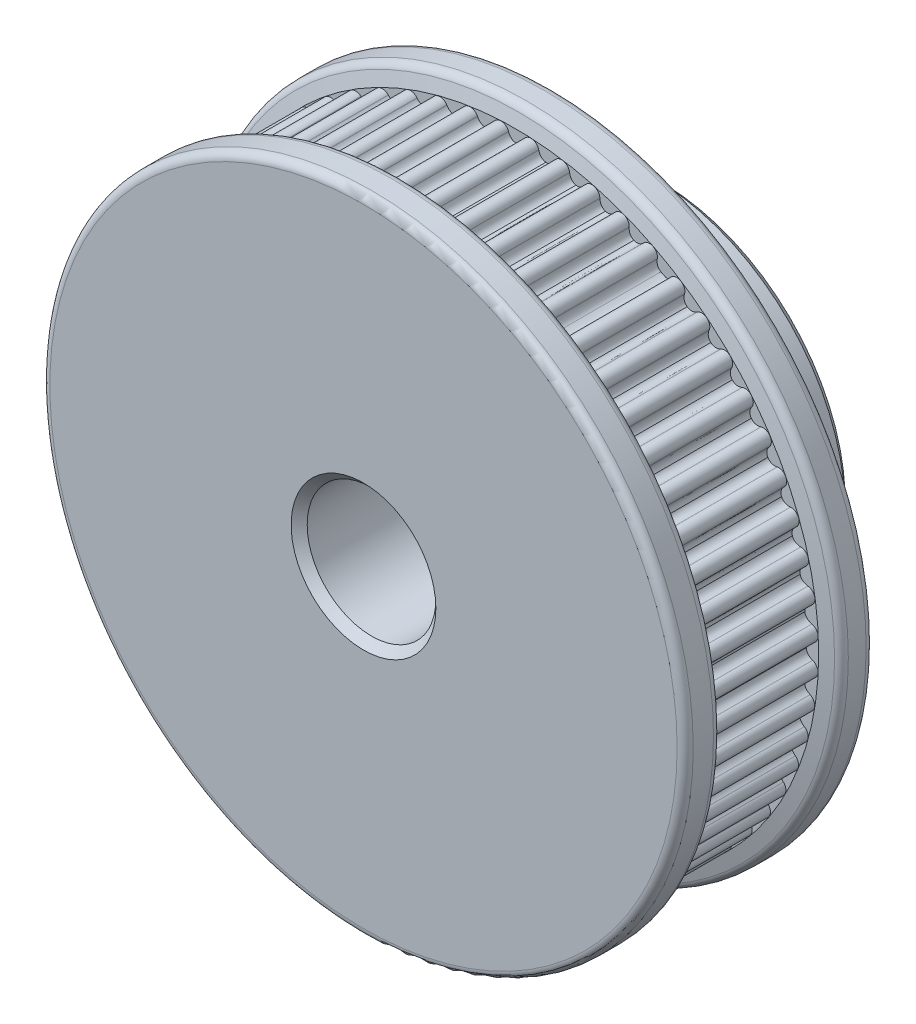
SolidWorks part; units mm, degrees
other "Camera1"
other "Camera2"
other "Camera3"
ref_plane "Front" through (0, 0, 0) normal (0, 0, 1) x (1, 0, 0)
ref_plane "Top" through (0, 0, 0) normal (0, 1, 0) x (1, 0, 0)
ref_plane "Right" through (0, 0, 0) normal (1, 0, 0) x (0, 0, -1)
sketch "Sketch1" plane through (0, 0, 0) normal (1, 0, 0) x (0, 0, -1)
  line L0 (0, 0) -> (-24.4032, 0) construction
  line L1 (0, 4) -> (0, 12)
  line L2 (0, 12) -> (-7, 12)
  line L3 (-7, 12) -> (-7, 18.3141)
  line L4 (-9, 18.85) -> (-16, 18.85)
  line L5 (-18, 18.3141) -> (-18, 4) construction
  line L6 (-18, 4) -> (0, 4)
  line L7 (-7, 18.3141) -> (-6.5483, 20)
  line L9 (-8.6919, 20) -> (-9, 18.85)
  line L10 (-18, 13.3586) -> (-7, 13.3586) construction
  line L11 (-12.5, 18.85) -> (-12.5, 22.0506) construction
  line L12 (-16.3081, 20) -> (-16, 18.85)
  line L14 (-18, 18.3141) -> (-18.4517, 20) construction
  line L15 (-18, 18.3141) -> (-16, 18.85) construction
  line L16 (-9, 18.85) -> (-7, 18.3141) construction
  line L17 (-18.4517, 20) -> (-16.3081, 20)
  line L18 (-8.6919, 20) -> (-6.5483, 20)
  line L19 (-18.4517, 20) -> (-18.4517, 4)
  line L20 (-18.4517, 4) -> (-18, 4)
  circle A0 centre (-3.5, 4) radius 2 construction
  point P22 (-3.5, 12)
  point P24 (-12.5, 13.3586)
  dimension "D9" = 4
  dimension "D1" = 18
  dimension "D2" = 11
  dimension "D3" = 7
  dimension "D4" = 37.7
  dimension "D5" = 40
  dimension "D6" = 15
  dimension "D7" = 24
  dimension "D8" = 8
revolve "Revolve1" add sketch "Sketch1" angle 360 about L0
ref_plane "Plane2" through (0, 0, 9) normal (0, 0, 1) x (1, 0, 0)
ref_plane "Plane3" through (0, 0, 16) normal (0, 0, 1) x (1, 0, 0)
sketch "Sketch3" plane through (0, 0, 9) normal (0, 0, 1) x (1, 0, 0)
  line L0 (0.4895, 18.4804) -> (0.4858, 18.4697)
  line L1 (-0.4323, 18.471) -> (-0.436, 18.4817)
  line L2 (-1.3914, 18.4344) -> (-1.394, 18.4234)
  line L3 (-2.3607, 18.3247) -> (-2.3654, 18.3349)
  line L4 (-3.3107, 18.188) -> (-3.3122, 18.1768)
  line L5 (-4.2632, 17.9775) -> (-4.269, 17.9872)
  line L6 (-5.1937, 17.7423) -> (-5.194, 17.731)
  line L7 (-6.119, 17.4334) -> (-6.1258, 17.4424)
  line L8 (-7.0199, 17.1022) -> (-7.019, 17.0909)
  line L9 (-7.9078, 16.6983) -> (-7.9155, 16.7066)
  line L10 (-8.7691, 16.2747) -> (-8.767, 16.2636)
  line L11 (-9.6099, 15.7803) -> (-9.6184, 15.7877)
  line L12 (-10.4222, 15.269) -> (-10.419, 15.2581)
  line L13 (-11.2067, 14.6893) -> (-11.216, 14.6958)
  line L14 (-11.9612, 14.0959) -> (-11.9568, 14.0855)
  line L15 (-12.6808, 13.4374) -> (-12.6907, 13.4429)
  line L16 (-13.3691, 12.7684) -> (-13.3637, 12.7585)
  line L17 (-14.0159, 12.0383) -> (-14.0263, 12.0427)
  line L18 (-14.6305, 11.301) -> (-14.6241, 11.2917)
  line L19 (-15.1975, 10.5073) -> (-15.2083, 10.5106)
  line L20 (-15.7316, 9.7098) -> (-15.7243, 9.7012)
  line L21 (-16.2125, 8.8612) -> (-16.2236, 8.8633)
  line L22 (-16.6604, 8.0122) -> (-16.6522, 8.0044)
  line L23 (-17.05, 7.118) -> (-17.0612, 7.1189)
  line L24 (-17.4066, 6.2268) -> (-17.3977, 6.22)
  line L25 (-17.7006, 5.2968) -> (-17.7119, 5.2965)
  line L26 (-17.9621, 4.3732) -> (-17.9525, 4.3673)
  line L27 (-18.1573, 3.4175) -> (-18.1685, 3.4161)
  line L28 (-18.3209, 2.4717) -> (-18.3107, 2.4669)
  line L29 (-18.415, 1.5008) -> (-18.426, 1.4983)
  line L30 (-18.4789, 0.5431) -> (-18.4682, 0.5394)
  line L31 (-18.471, -0.4323) -> (-18.4817, -0.436)
  line L32 (-18.4344, -1.3914) -> (-18.4234, -1.394)
  line L33 (-18.3247, -2.3607) -> (-18.3349, -2.3654)
  line L34 (-18.188, -3.3107) -> (-18.1768, -3.3122)
  line L35 (-17.9775, -4.2632) -> (-17.9872, -4.269)
  line L36 (-17.7423, -5.1937) -> (-17.731, -5.194)
  line L37 (-17.4334, -6.119) -> (-17.4424, -6.1258)
  line L38 (-17.1022, -7.0199) -> (-17.0909, -7.019)
  line L39 (-16.6983, -7.9078) -> (-16.7066, -7.9155)
  line L40 (-16.2747, -8.7691) -> (-16.2636, -8.767)
  line L41 (-15.7803, -9.6099) -> (-15.7877, -9.6184)
  line L42 (-15.269, -10.4222) -> (-15.2581, -10.419)
  line L43 (-14.6893, -11.2067) -> (-14.6958, -11.216)
  line L44 (-14.0959, -11.9612) -> (-14.0855, -11.9568)
  line L45 (-13.4374, -12.6808) -> (-13.4429, -12.6907)
  line L46 (-12.7684, -13.3691) -> (-12.7585, -13.3637)
  line L47 (-12.0383, -14.0159) -> (-12.0427, -14.0263)
  line L48 (-11.301, -14.6305) -> (-11.2917, -14.6241)
  line L49 (-10.5073, -15.1975) -> (-10.5106, -15.2083)
  line L50 (-9.7098, -15.7316) -> (-9.7012, -15.7243)
  line L51 (-8.8612, -16.2125) -> (-8.8633, -16.2236)
  line L52 (-8.0122, -16.6604) -> (-8.0044, -16.6522)
  line L53 (-7.118, -17.05) -> (-7.1189, -17.0612)
  line L54 (-6.2268, -17.4066) -> (-6.22, -17.3977)
  line L55 (-5.2968, -17.7006) -> (-5.2965, -17.7119)
  line L56 (-4.3732, -17.9621) -> (-4.3673, -17.9525)
  line L57 (-3.4175, -18.1573) -> (-3.4161, -18.1685)
  line L58 (-2.4717, -18.3209) -> (-2.4669, -18.3107)
  line L59 (-1.5008, -18.415) -> (-1.4983, -18.426)
  line L60 (-0.5431, -18.4789) -> (-0.5394, -18.4682)
  line L61 (0.4323, -18.471) -> (0.436, -18.4817)
  line L62 (1.3914, -18.4344) -> (1.394, -18.4234)
  line L63 (2.3607, -18.3247) -> (2.3654, -18.3349)
  line L64 (3.3107, -18.188) -> (3.3122, -18.1768)
  line L65 (4.2632, -17.9775) -> (4.269, -17.9872)
  line L66 (5.1937, -17.7423) -> (5.194, -17.731)
  line L67 (6.119, -17.4334) -> (6.1258, -17.4424)
  line L68 (7.0199, -17.1022) -> (7.019, -17.0909)
  line L69 (7.9078, -16.6983) -> (7.9155, -16.7066)
  line L70 (8.7691, -16.2747) -> (8.767, -16.2636)
  line L71 (9.6099, -15.7803) -> (9.6184, -15.7877)
  line L72 (10.4222, -15.269) -> (10.419, -15.2581)
  line L73 (11.2067, -14.6893) -> (11.216, -14.6958)
  line L74 (11.9612, -14.0959) -> (11.9568, -14.0855)
  line L75 (12.6808, -13.4374) -> (12.6907, -13.4429)
  line L76 (13.3691, -12.7684) -> (13.3637, -12.7585)
  line L77 (14.0159, -12.0383) -> (14.0263, -12.0427)
  line L78 (14.6305, -11.301) -> (14.6241, -11.2917)
  line L79 (15.1975, -10.5073) -> (15.2083, -10.5106)
  line L80 (15.7316, -9.7098) -> (15.7243, -9.7012)
  line L81 (16.2125, -8.8612) -> (16.2236, -8.8633)
  line L82 (16.6604, -8.0122) -> (16.6522, -8.0044)
  line L83 (17.05, -7.118) -> (17.0612, -7.1189)
  line L84 (17.4066, -6.2268) -> (17.3977, -6.22)
  line L85 (17.7006, -5.2968) -> (17.7119, -5.2965)
  line L86 (17.9621, -4.3732) -> (17.9525, -4.3673)
  line L87 (18.1573, -3.4175) -> (18.1685, -3.4161)
  line L88 (18.3209, -2.4717) -> (18.3107, -2.4669)
  line L89 (18.415, -1.5008) -> (18.426, -1.4983)
  line L90 (18.4789, -0.5431) -> (18.4682, -0.5394)
  line L91 (18.471, 0.4323) -> (18.4817, 0.436)
  line L92 (18.4344, 1.3914) -> (18.4234, 1.394)
  line L93 (18.3247, 2.3607) -> (18.3349, 2.3654)
  line L94 (18.188, 3.3107) -> (18.1768, 3.3122)
  line L95 (17.9775, 4.2632) -> (17.9872, 4.269)
  line L96 (17.7423, 5.1937) -> (17.731, 5.194)
  line L97 (17.4334, 6.119) -> (17.4424, 6.1258)
  line L98 (17.1022, 7.0199) -> (17.0909, 7.019)
  line L99 (16.6983, 7.9078) -> (16.7066, 7.9155)
  line L100 (16.2747, 8.7691) -> (16.2636, 8.767)
  line L101 (15.7803, 9.6099) -> (15.7877, 9.6184)
  line L102 (15.269, 10.4222) -> (15.2581, 10.419)
  line L103 (14.6893, 11.2067) -> (14.6958, 11.216)
  line L104 (14.0959, 11.9612) -> (14.0855, 11.9568)
  line L105 (13.4374, 12.6808) -> (13.4429, 12.6907)
  line L106 (12.7684, 13.3691) -> (12.7585, 13.3637)
  line L107 (12.0383, 14.0159) -> (12.0427, 14.0263)
  line L108 (11.301, 14.6305) -> (11.2917, 14.6241)
  line L109 (10.5073, 15.1975) -> (10.5106, 15.2083)
  line L110 (9.7098, 15.7316) -> (9.7012, 15.7243)
  line L111 (8.8141, 16.2382) -> (8.8162, 16.2492)
  line L112 (7.9639, 16.6835) -> (7.9561, 16.6753)
  line L113 (7.0685, 17.0705) -> (7.0694, 17.0818)
  line L114 (6.1763, 17.4246) -> (6.1695, 17.4156)
  line L115 (5.2454, 17.7159) -> (5.2452, 17.7272)
  line L116 (4.3211, 17.9748) -> (4.3153, 17.9651)
  line L117 (3.3649, 18.1671) -> (3.3634, 18.1783)
  line L118 (2.4186, 18.328) -> (2.4138, 18.3178)
  line L119 (1.4475, 18.4193) -> (1.4449, 18.4303)
  arc A0 (-0.436, 18.4817) -> (-1.3914, 18.4344) centre (-0.9065, 18.3126) ccw
  arc A1 (-2.3654, 18.3349) -> (-3.3107, 18.188) centre (-2.8157, 18.1175) ccw
  arc A2 (-4.269, 17.9872) -> (-5.1937, 17.7423) centre (-4.6941, 17.7239) ccw
  arc A3 (-6.1258, 17.4424) -> (-7.0199, 17.1022) centre (-6.521, 17.1362) ccw
  arc A4 (-7.9155, 16.7066) -> (-8.7691, 16.2747) centre (-8.2765, 16.3607) ccw
  arc A5 (-9.6184, 15.7877) -> (-10.4222, 15.269) centre (-9.9413, 15.4059) ccw
  arc A6 (-11.216, 14.6958) -> (-11.9612, 14.0959) centre (-11.4972, 14.2824) ccw
  arc A7 (-12.6907, 13.4429) -> (-13.3691, 12.7684) centre (-12.9272, 13.0023) ccw
  arc A8 (-14.0263, 12.0427) -> (-14.6305, 11.301) centre (-14.2155, 11.5798) ccw
  arc A9 (-15.2083, 10.5106) -> (-15.7316, 9.7098) centre (-15.348, 10.0305) ccw
  arc A10 (-16.2236, 8.8633) -> (-16.6604, 8.0122) centre (-16.3124, 8.3712) ccw
  arc A11 (-17.0612, 7.1189) -> (-17.4066, 6.2268) centre (-17.0981, 6.6203) ccw
  arc A12 (-17.7119, 5.2965) -> (-17.9621, 4.3732) centre (-17.6964, 4.7968) ccw
  arc A13 (-18.1685, 3.4161) -> (-18.3209, 2.4717) centre (-18.1009, 2.9207) ccw
  arc A14 (-18.426, 1.4983) -> (-18.4789, 0.5431) centre (-18.307, 1.0127) ccw
  arc A15 (-18.4817, -0.436) -> (-18.4344, -1.3914) centre (-18.3126, -0.9065) ccw
  arc A16 (-18.3349, -2.3654) -> (-18.188, -3.3107) centre (-18.1175, -2.8157) ccw
  arc A17 (-17.9872, -4.269) -> (-17.7423, -5.1937) centre (-17.7239, -4.6941) ccw
  arc A18 (-17.4424, -6.1258) -> (-17.1022, -7.0199) centre (-17.1362, -6.521) ccw
  arc A19 (-16.7066, -7.9155) -> (-16.2747, -8.7691) centre (-16.3607, -8.2765) ccw
  arc A20 (-15.7877, -9.6184) -> (-15.269, -10.4222) centre (-15.4059, -9.9413) ccw
  arc A21 (-14.6958, -11.216) -> (-14.0959, -11.9612) centre (-14.2824, -11.4972) ccw
  arc A22 (-13.4429, -12.6907) -> (-12.7684, -13.3691) centre (-13.0023, -12.9272) ccw
  arc A23 (-12.0427, -14.0263) -> (-11.301, -14.6305) centre (-11.5798, -14.2155) ccw
  arc A24 (-10.5106, -15.2083) -> (-9.7098, -15.7316) centre (-10.0305, -15.348) ccw
  arc A25 (-8.8633, -16.2236) -> (-8.0122, -16.6604) centre (-8.3712, -16.3124) ccw
  arc A26 (-7.1189, -17.0612) -> (-6.2268, -17.4066) centre (-6.6203, -17.0981) ccw
  arc A27 (-5.2965, -17.7119) -> (-4.3732, -17.9621) centre (-4.7968, -17.6964) ccw
  arc A28 (-3.4161, -18.1685) -> (-2.4717, -18.3209) centre (-2.9207, -18.1009) ccw
  arc A29 (-1.4983, -18.426) -> (-0.5431, -18.4789) centre (-1.0127, -18.307) ccw
  arc A30 (0.436, -18.4817) -> (1.3914, -18.4344) centre (0.9065, -18.3126) ccw
  arc A31 (2.3654, -18.3349) -> (3.3107, -18.188) centre (2.8157, -18.1175) ccw
  arc A32 (4.269, -17.9872) -> (5.1937, -17.7423) centre (4.6941, -17.7239) ccw
  arc A33 (6.1258, -17.4424) -> (7.0199, -17.1022) centre (6.521, -17.1362) ccw
  arc A34 (7.9155, -16.7066) -> (8.7691, -16.2747) centre (8.2765, -16.3607) ccw
  arc A35 (9.6184, -15.7877) -> (10.4222, -15.269) centre (9.9413, -15.4059) ccw
  arc A36 (11.216, -14.6958) -> (11.9612, -14.0959) centre (11.4972, -14.2824) ccw
  arc A37 (12.6907, -13.4429) -> (13.3691, -12.7684) centre (12.9272, -13.0023) ccw
  arc A38 (14.0263, -12.0427) -> (14.6305, -11.301) centre (14.2155, -11.5798) ccw
  arc A39 (15.2083, -10.5106) -> (15.7316, -9.7098) centre (15.348, -10.0305) ccw
  arc A40 (16.2236, -8.8633) -> (16.6604, -8.0122) centre (16.3124, -8.3712) ccw
  arc A41 (17.0612, -7.1189) -> (17.4066, -6.2268) centre (17.0981, -6.6203) ccw
  arc A42 (17.7119, -5.2965) -> (17.9621, -4.3732) centre (17.6964, -4.7968) ccw
  arc A43 (18.1685, -3.4161) -> (18.3209, -2.4717) centre (18.1009, -2.9207) ccw
  arc A44 (18.426, -1.4983) -> (18.4789, -0.5431) centre (18.307, -1.0127) ccw
  arc A45 (18.4817, 0.436) -> (18.4344, 1.3914) centre (18.3126, 0.9065) ccw
  arc A46 (18.3349, 2.3654) -> (18.188, 3.3107) centre (18.1175, 2.8157) ccw
  arc A47 (17.9872, 4.269) -> (17.7423, 5.1937) centre (17.7239, 4.6941) ccw
  arc A48 (17.4424, 6.1258) -> (17.1022, 7.0199) centre (17.1362, 6.521) ccw
  arc A49 (16.7066, 7.9155) -> (16.2747, 8.7691) centre (16.3607, 8.2765) ccw
  arc A50 (15.7877, 9.6184) -> (15.269, 10.4222) centre (15.4059, 9.9413) ccw
  arc A51 (14.6958, 11.216) -> (14.0959, 11.9612) centre (14.2824, 11.4972) ccw
  arc A52 (13.4429, 12.6907) -> (12.7684, 13.3691) centre (13.0023, 12.9272) ccw
  arc A53 (12.0427, 14.0263) -> (11.301, 14.6305) centre (11.5798, 14.2155) ccw
  arc A54 (10.5106, 15.2083) -> (9.7098, 15.7316) centre (10.0305, 15.348) ccw
  arc A55 (8.8162, 16.2492) -> (7.9639, 16.6835) centre (8.3239, 16.3366) ccw
  arc A56 (7.0694, 17.0818) -> (6.1763, 17.4246) centre (6.5707, 17.1172) ccw
  arc A57 (5.2452, 17.7272) -> (4.3211, 17.9748) centre (4.7454, 17.7103) ccw
  arc A58 (3.3634, 18.1783) -> (2.4186, 18.328) centre (2.8682, 18.1093) ccw
  arc A59 (1.4449, 18.4303) -> (0.4895, 18.4804) centre (0.9596, 18.3099) ccw
  spline S0 degree 3 poles (0.4858, 18.4697) (0.4077, 18.2495) (0.2403, 18.0862) (0.0262, 18.0851) knots 0 0 0 0 1 1 1 1
  spline S1 degree 3 poles (0.0262, 18.0851) (-0.1878, 18.0868) (-0.3548, 18.2506) (-0.4323, 18.471) knots 0 0 0 0 1 1 1 1
  spline S2 degree 3 poles (-1.394, 18.4234) (-1.4515, 18.1875) (-1.5982, 18.0156) (-1.8382, 17.9913) knots 0 0 0 0 1 1 1 1
  spline S3 degree 3 poles (-1.8382, 17.9913) (-2.0782, 17.9665) (-2.2567, 18.1053) (-2.3607, 18.3247) knots 0 0 0 0 1 1 1 1
  spline S4 degree 3 poles (-3.3122, 18.1768) (-3.3447, 17.9362) (-3.4726, 17.7498) (-3.7088, 17.7006) knots 0 0 0 0 1 1 1 1
  spline S5 degree 3 poles (-3.7088, 17.7006) (-3.9448, 17.6509) (-4.1368, 17.7702) (-4.2632, 17.9775) knots 0 0 0 0 1 1 1 1
  spline S6 degree 3 poles (-5.194, 17.731) (-5.2012, 17.4883) (-5.309, 17.2896) (-5.5387, 17.216) knots 0 0 0 0 1 1 1 1
  spline S7 degree 3 poles (-5.5387, 17.216) (-5.7682, 17.1418) (-5.9717, 17.2404) (-6.119, 17.4334) knots 0 0 0 0 1 1 1 1
  spline S8 degree 3 poles (-7.019, 17.0909) (-7.0007, 16.8488) (-7.0871, 16.6399) (-7.3079, 16.5427) knots 0 0 0 0 1 1 1 1
  spline S9 degree 3 poles (-7.3079, 16.5427) (-7.5284, 16.445) (-7.7411, 16.5218) (-7.9078, 16.6983) knots 0 0 0 0 1 1 1 1
  spline S10 degree 3 poles (-8.767, 16.2636) (-8.7236, 16.0248) (-8.7877, 15.808) (-8.9971, 15.6882) knots 0 0 0 0 1 1 1 1
  spline S11 degree 3 poles (-8.9971, 15.6882) (-9.2062, 15.568) (-9.4256, 15.6221) (-9.6099, 15.7803) knots 0 0 0 0 1 1 1 1
  spline S12 degree 3 poles (-10.419, 15.2581) (-10.3508, 15.0251) (-10.3919, 14.8028) (-10.5876, 14.6618) knots 0 0 0 0 1 1 1 1
  spline S13 degree 3 poles (-10.5876, 14.6618) (-10.783, 14.5204) (-11.007, 14.5513) (-11.2067, 14.6893) knots 0 0 0 0 1 1 1 1
  spline S14 degree 3 poles (-11.9568, 14.0855) (-11.8647, 13.8608) (-11.8823, 13.6355) (-12.0622, 13.4748) knots 0 0 0 0 1 1 1 1
  spline S15 degree 3 poles (-12.0622, 13.4748) (-12.2418, 13.3137) (-12.4677, 13.321) (-12.6808, 13.4374) knots 0 0 0 0 1 1 1 1
  spline S16 degree 3 poles (-13.3637, 12.7585) (-13.2485, 12.5447) (-13.2425, 12.3187) (-13.4046, 12.1401) knots 0 0 0 0 1 1 1 1
  spline S17 degree 3 poles (-13.4046, 12.1401) (-13.5664, 11.9611) (-13.7918, 11.9448) (-14.0159, 12.0383) knots 0 0 0 0 1 1 1 1
  spline S18 degree 3 poles (-14.6241, 11.2917) (-14.4872, 11.0912) (-14.4576, 10.867) (-14.6002, 10.6725) knots 0 0 0 0 1 1 1 1
  spline S19 degree 3 poles (-14.6002, 10.6725) (-14.7423, 10.4776) (-14.9648, 10.4378) (-15.1975, 10.5073) knots 0 0 0 0 1 1 1 1
  spline S20 degree 3 poles (-15.7243, 9.7012) (-15.5672, 9.5161) (-15.5143, 9.2963) (-15.6358, 9.0879) knots 0 0 0 0 1 1 1 1
  spline S21 degree 3 poles (-15.6358, 9.0879) (-15.7568, 8.8792) (-15.9739, 8.8163) (-16.2125, 8.8612) knots 0 0 0 0 1 1 1 1
  spline S22 degree 3 poles (-16.6522, 8.0044) (-16.4766, 7.8367) (-16.4011, 7.6237) (-16.5001, 7.4037) knots 0 0 0 0 1 1 1 1
  spline S23 degree 3 poles (-16.5001, 7.4037) (-16.5986, 7.1835) (-16.808, 7.0983) (-17.05, 7.118) knots 0 0 0 0 1 1 1 1
  spline S24 degree 3 poles (-17.3977, 6.22) (-17.2055, 6.0715) (-17.1081, 5.8675) (-17.1836, 5.6384) knots 0 0 0 0 1 1 1 1
  spline S25 degree 3 poles (-17.1836, 5.6384) (-17.2585, 5.4091) (-17.4579, 5.3025) (-17.7006, 5.2968) knots 0 0 0 0 1 1 1 1
  spline S26 degree 3 poles (-17.9525, 4.3673) (-17.7459, 4.2398) (-17.6277, 4.0471) (-17.6788, 3.8114) knots 0 0 0 0 1 1 1 1
  spline S27 degree 3 poles (-17.6788, 3.8114) (-17.7294, 3.5755) (-17.9165, 3.4486) (-18.1573, 3.4175) knots 0 0 0 0 1 1 1 1
  spline S28 degree 3 poles (-18.3107, 2.4669) (-18.0919, 2.3616) (-17.9542, 2.1823) (-17.9804, 1.9425) knots 0 0 0 0 1 1 1 1
  spline S29 degree 3 poles (-17.9804, 1.9425) (-18.006, 1.7027) (-18.1788, 1.5569) (-18.415, 1.5008) knots 0 0 0 0 1 1 1 1
  spline S30 degree 3 poles (-18.4682, 0.5394) (-18.2396, 0.4576) (-18.0839, 0.2937) (-18.0849, 0.0524) knots 0 0 0 0 1 1 1 1
  spline S31 degree 3 poles (-18.0849, 0.0524) (-18.0853, -0.1888) (-18.242, -0.3518) (-18.471, -0.4323) knots 0 0 0 0 1 1 1 1
  spline S32 degree 3 poles (-18.4234, -1.394) (-18.1875, -1.4515) (-18.0156, -1.5982) (-17.9913, -1.8382) knots 0 0 0 0 1 1 1 1
  spline S33 degree 3 poles (-17.9913, -1.8382) (-17.9665, -2.0782) (-18.1053, -2.2567) (-18.3247, -2.3607) knots 0 0 0 0 1 1 1 1
  spline S34 degree 3 poles (-18.1768, -3.3122) (-17.9362, -3.3447) (-17.7498, -3.4726) (-17.7006, -3.7088) knots 0 0 0 0 1 1 1 1
  spline S35 degree 3 poles (-17.7006, -3.7088) (-17.6509, -3.9448) (-17.7702, -4.1368) (-17.9775, -4.2632) knots 0 0 0 0 1 1 1 1
  spline S36 degree 3 poles (-17.731, -5.194) (-17.4883, -5.2012) (-17.2896, -5.309) (-17.216, -5.5387) knots 0 0 0 0 1 1 1 1
  spline S37 degree 3 poles (-17.216, -5.5387) (-17.1418, -5.7682) (-17.2404, -5.9717) (-17.4334, -6.119) knots 0 0 0 0 1 1 1 1
  spline S38 degree 3 poles (-17.0909, -7.019) (-16.8488, -7.0007) (-16.6399, -7.0871) (-16.5427, -7.3079) knots 0 0 0 0 1 1 1 1
  spline S39 degree 3 poles (-16.5427, -7.3079) (-16.445, -7.5284) (-16.5218, -7.7411) (-16.6983, -7.9078) knots 0 0 0 0 1 1 1 1
  spline S40 degree 3 poles (-16.2636, -8.767) (-16.0248, -8.7236) (-15.808, -8.7877) (-15.6882, -8.9971) knots 0 0 0 0 1 1 1 1
  spline S41 degree 3 poles (-15.6882, -8.9971) (-15.568, -9.2062) (-15.6221, -9.4256) (-15.7803, -9.6099) knots 0 0 0 0 1 1 1 1
  spline S42 degree 3 poles (-15.2581, -10.419) (-15.0251, -10.3508) (-14.8028, -10.3919) (-14.6618, -10.5876) knots 0 0 0 0 1 1 1 1
  spline S43 degree 3 poles (-14.6618, -10.5876) (-14.5204, -10.783) (-14.5513, -11.007) (-14.6893, -11.2067) knots 0 0 0 0 1 1 1 1
  spline S44 degree 3 poles (-14.0855, -11.9568) (-13.8608, -11.8647) (-13.6355, -11.8823) (-13.4748, -12.0622) knots 0 0 0 0 1 1 1 1
  spline S45 degree 3 poles (-13.4748, -12.0622) (-13.3137, -12.2418) (-13.321, -12.4677) (-13.4374, -12.6808) knots 0 0 0 0 1 1 1 1
  spline S46 degree 3 poles (-12.7585, -13.3637) (-12.5447, -13.2485) (-12.3187, -13.2425) (-12.1401, -13.4046) knots 0 0 0 0 1 1 1 1
  spline S47 degree 3 poles (-12.1401, -13.4046) (-11.9611, -13.5664) (-11.9448, -13.7918) (-12.0383, -14.0159) knots 0 0 0 0 1 1 1 1
  spline S48 degree 3 poles (-11.2917, -14.6241) (-11.0912, -14.4872) (-10.867, -14.4576) (-10.6725, -14.6002) knots 0 0 0 0 1 1 1 1
  spline S49 degree 3 poles (-10.6725, -14.6002) (-10.4776, -14.7423) (-10.4378, -14.9648) (-10.5073, -15.1975) knots 0 0 0 0 1 1 1 1
  spline S50 degree 3 poles (-9.7012, -15.7243) (-9.5161, -15.5672) (-9.2963, -15.5143) (-9.0879, -15.6358) knots 0 0 0 0 1 1 1 1
  spline S51 degree 3 poles (-9.0879, -15.6358) (-8.8792, -15.7568) (-8.8163, -15.9739) (-8.8612, -16.2125) knots 0 0 0 0 1 1 1 1
  spline S52 degree 3 poles (-8.0044, -16.6522) (-7.8367, -16.4766) (-7.6237, -16.4011) (-7.4037, -16.5001) knots 0 0 0 0 1 1 1 1
  spline S53 degree 3 poles (-7.4037, -16.5001) (-7.1835, -16.5986) (-7.0983, -16.808) (-7.118, -17.05) knots 0 0 0 0 1 1 1 1
  spline S54 degree 3 poles (-6.22, -17.3977) (-6.0715, -17.2055) (-5.8675, -17.1081) (-5.6384, -17.1836) knots 0 0 0 0 1 1 1 1
  spline S55 degree 3 poles (-5.6384, -17.1836) (-5.4091, -17.2585) (-5.3025, -17.4579) (-5.2968, -17.7006) knots 0 0 0 0 1 1 1 1
  spline S56 degree 3 poles (-4.3673, -17.9525) (-4.2398, -17.7459) (-4.0471, -17.6277) (-3.8114, -17.6788) knots 0 0 0 0 1 1 1 1
  spline S57 degree 3 poles (-3.8114, -17.6788) (-3.5755, -17.7294) (-3.4486, -17.9165) (-3.4175, -18.1573) knots 0 0 0 0 1 1 1 1
  spline S58 degree 3 poles (-2.4669, -18.3107) (-2.3616, -18.0919) (-2.1823, -17.9542) (-1.9425, -17.9804) knots 0 0 0 0 1 1 1 1
  spline S59 degree 3 poles (-1.9425, -17.9804) (-1.7027, -18.006) (-1.5569, -18.1788) (-1.5008, -18.415) knots 0 0 0 0 1 1 1 1
  spline S60 degree 3 poles (-0.5394, -18.4682) (-0.4576, -18.2396) (-0.2937, -18.0839) (-0.0524, -18.0849) knots 0 0 0 0 1 1 1 1
  spline S61 degree 3 poles (-0.0524, -18.0849) (0.1888, -18.0853) (0.3518, -18.242) (0.4323, -18.471) knots 0 0 0 0 1 1 1 1
  spline S62 degree 3 poles (1.394, -18.4234) (1.4515, -18.1875) (1.5982, -18.0156) (1.8382, -17.9913) knots 0 0 0 0 1 1 1 1
  spline S63 degree 3 poles (1.8382, -17.9913) (2.0782, -17.9665) (2.2567, -18.1053) (2.3607, -18.3247) knots 0 0 0 0 1 1 1 1
  spline S64 degree 3 poles (3.3122, -18.1768) (3.3447, -17.9362) (3.4726, -17.7498) (3.7088, -17.7006) knots 0 0 0 0 1 1 1 1
  spline S65 degree 3 poles (3.7088, -17.7006) (3.9448, -17.6509) (4.1368, -17.7702) (4.2632, -17.9775) knots 0 0 0 0 1 1 1 1
  spline S66 degree 3 poles (5.194, -17.731) (5.2012, -17.4883) (5.309, -17.2896) (5.5387, -17.216) knots 0 0 0 0 1 1 1 1
  spline S67 degree 3 poles (5.5387, -17.216) (5.7682, -17.1418) (5.9717, -17.2404) (6.119, -17.4334) knots 0 0 0 0 1 1 1 1
  spline S68 degree 3 poles (7.019, -17.0909) (7.0007, -16.8488) (7.0871, -16.6399) (7.3079, -16.5427) knots 0 0 0 0 1 1 1 1
  spline S69 degree 3 poles (7.3079, -16.5427) (7.5284, -16.445) (7.7411, -16.5218) (7.9078, -16.6983) knots 0 0 0 0 1 1 1 1
  spline S70 degree 3 poles (8.767, -16.2636) (8.7236, -16.0248) (8.7877, -15.808) (8.9971, -15.6882) knots 0 0 0 0 1 1 1 1
  spline S71 degree 3 poles (8.9971, -15.6882) (9.2062, -15.568) (9.4256, -15.6221) (9.6099, -15.7803) knots 0 0 0 0 1 1 1 1
  spline S72 degree 3 poles (10.419, -15.2581) (10.3508, -15.0251) (10.3919, -14.8028) (10.5876, -14.6618) knots 0 0 0 0 1 1 1 1
  spline S73 degree 3 poles (10.5876, -14.6618) (10.783, -14.5204) (11.007, -14.5513) (11.2067, -14.6893) knots 0 0 0 0 1 1 1 1
  spline S74 degree 3 poles (11.9568, -14.0855) (11.8647, -13.8608) (11.8823, -13.6355) (12.0622, -13.4748) knots 0 0 0 0 1 1 1 1
  spline S75 degree 3 poles (12.0622, -13.4748) (12.2418, -13.3137) (12.4677, -13.321) (12.6808, -13.4374) knots 0 0 0 0 1 1 1 1
  spline S76 degree 3 poles (13.3637, -12.7585) (13.2485, -12.5447) (13.2425, -12.3187) (13.4046, -12.1401) knots 0 0 0 0 1 1 1 1
  spline S77 degree 3 poles (13.4046, -12.1401) (13.5664, -11.9611) (13.7918, -11.9448) (14.0159, -12.0383) knots 0 0 0 0 1 1 1 1
  spline S78 degree 3 poles (14.6241, -11.2917) (14.4872, -11.0912) (14.4576, -10.867) (14.6002, -10.6725) knots 0 0 0 0 1 1 1 1
  spline S79 degree 3 poles (14.6002, -10.6725) (14.7423, -10.4776) (14.9648, -10.4378) (15.1975, -10.5073) knots 0 0 0 0 1 1 1 1
  spline S80 degree 3 poles (15.7243, -9.7012) (15.5672, -9.5161) (15.5143, -9.2963) (15.6358, -9.0879) knots 0 0 0 0 1 1 1 1
  spline S81 degree 3 poles (15.6358, -9.0879) (15.7568, -8.8792) (15.9739, -8.8163) (16.2125, -8.8612) knots 0 0 0 0 1 1 1 1
  spline S82 degree 3 poles (16.6522, -8.0044) (16.4766, -7.8367) (16.4011, -7.6237) (16.5001, -7.4037) knots 0 0 0 0 1 1 1 1
  spline S83 degree 3 poles (16.5001, -7.4037) (16.5986, -7.1835) (16.808, -7.0983) (17.05, -7.118) knots 0 0 0 0 1 1 1 1
  spline S84 degree 3 poles (17.3977, -6.22) (17.2055, -6.0715) (17.1081, -5.8675) (17.1836, -5.6384) knots 0 0 0 0 1 1 1 1
  spline S85 degree 3 poles (17.1836, -5.6384) (17.2585, -5.4091) (17.4579, -5.3025) (17.7006, -5.2968) knots 0 0 0 0 1 1 1 1
  spline S86 degree 3 poles (17.9525, -4.3673) (17.7459, -4.2398) (17.6277, -4.0471) (17.6788, -3.8114) knots 0 0 0 0 1 1 1 1
  spline S87 degree 3 poles (17.6788, -3.8114) (17.7294, -3.5755) (17.9165, -3.4486) (18.1573, -3.4175) knots 0 0 0 0 1 1 1 1
  spline S88 degree 3 poles (18.3107, -2.4669) (18.0919, -2.3616) (17.9542, -2.1823) (17.9804, -1.9425) knots 0 0 0 0 1 1 1 1
  spline S89 degree 3 poles (17.9804, -1.9425) (18.006, -1.7027) (18.1788, -1.5569) (18.415, -1.5008) knots 0 0 0 0 1 1 1 1
  spline S90 degree 3 poles (18.4682, -0.5394) (18.2396, -0.4576) (18.0839, -0.2937) (18.0849, -0.0524) knots 0 0 0 0 1 1 1 1
  spline S91 degree 3 poles (18.0849, -0.0524) (18.0853, 0.1888) (18.242, 0.3518) (18.471, 0.4323) knots 0 0 0 0 1 1 1 1
  spline S92 degree 3 poles (18.4234, 1.394) (18.1875, 1.4515) (18.0156, 1.5982) (17.9913, 1.8382) knots 0 0 0 0 1 1 1 1
  spline S93 degree 3 poles (17.9913, 1.8382) (17.9665, 2.0782) (18.1053, 2.2567) (18.3247, 2.3607) knots 0 0 0 0 1 1 1 1
  spline S94 degree 3 poles (18.1768, 3.3122) (17.9362, 3.3447) (17.7498, 3.4726) (17.7006, 3.7088) knots 0 0 0 0 1 1 1 1
  spline S95 degree 3 poles (17.7006, 3.7088) (17.6509, 3.9448) (17.7702, 4.1368) (17.9775, 4.2632) knots 0 0 0 0 1 1 1 1
  spline S96 degree 3 poles (17.731, 5.194) (17.4883, 5.2012) (17.2896, 5.309) (17.216, 5.5387) knots 0 0 0 0 1 1 1 1
  spline S97 degree 3 poles (17.216, 5.5387) (17.1418, 5.7682) (17.2404, 5.9717) (17.4334, 6.119) knots 0 0 0 0 1 1 1 1
  spline S98 degree 3 poles (17.0909, 7.019) (16.8488, 7.0007) (16.6399, 7.0871) (16.5427, 7.3079) knots 0 0 0 0 1 1 1 1
  spline S99 degree 3 poles (16.5427, 7.3079) (16.445, 7.5284) (16.5218, 7.7411) (16.6983, 7.9078) knots 0 0 0 0 1 1 1 1
  spline S100 degree 3 poles (16.2636, 8.767) (16.0248, 8.7236) (15.808, 8.7877) (15.6882, 8.9971) knots 0 0 0 0 1 1 1 1
  spline S101 degree 3 poles (15.6882, 8.9971) (15.568, 9.2062) (15.6221, 9.4256) (15.7803, 9.6099) knots 0 0 0 0 1 1 1 1
  spline S102 degree 3 poles (15.2581, 10.419) (15.0251, 10.3508) (14.8028, 10.3919) (14.6618, 10.5876) knots 0 0 0 0 1 1 1 1
  spline S103 degree 3 poles (14.6618, 10.5876) (14.5204, 10.783) (14.5513, 11.007) (14.6893, 11.2067) knots 0 0 0 0 1 1 1 1
  spline S104 degree 3 poles (14.0855, 11.9568) (13.8608, 11.8647) (13.6355, 11.8823) (13.4748, 12.0622) knots 0 0 0 0 1 1 1 1
  spline S105 degree 3 poles (13.4748, 12.0622) (13.3137, 12.2418) (13.321, 12.4677) (13.4374, 12.6808) knots 0 0 0 0 1 1 1 1
  spline S106 degree 3 poles (12.7585, 13.3637) (12.5447, 13.2485) (12.3187, 13.2425) (12.1401, 13.4046) knots 0 0 0 0 1 1 1 1
  spline S107 degree 3 poles (12.1401, 13.4046) (11.9611, 13.5664) (11.9448, 13.7918) (12.0383, 14.0159) knots 0 0 0 0 1 1 1 1
  spline S108 degree 3 poles (11.2917, 14.6241) (11.0912, 14.4872) (10.867, 14.4576) (10.6725, 14.6002) knots 0 0 0 0 1 1 1 1
  spline S109 degree 3 poles (10.6725, 14.6002) (10.4776, 14.7423) (10.4378, 14.9648) (10.5073, 15.1975) knots 0 0 0 0 1 1 1 1
  spline S110 degree 3 poles (9.7012, 15.7243) (9.5161, 15.5672) (9.5993, 15.3388) (9.0425, 15.6621) knots 0 0 0 0 1 1 1 1
  spline S111 degree 3 poles (9.0425, 15.6621) (8.8334, 15.7824) (8.77, 15.9994) (8.8141, 16.2382) knots 0 0 0 0 1 1 1 1
  spline S112 degree 3 poles (7.9561, 16.6753) (7.7889, 16.4993) (7.5761, 16.4231) (7.3558, 16.5215) knots 0 0 0 0 1 1 1 1
  spline S113 degree 3 poles (7.3558, 16.5215) (7.1353, 16.6193) (7.0495, 16.8285) (7.0685, 17.0705) knots 0 0 0 0 1 1 1 1
  spline S114 degree 3 poles (6.1695, 17.4156) (6.0216, 17.2231) (5.8179, 17.125) (5.5886, 17.1999) knots 0 0 0 0 1 1 1 1
  spline S115 degree 3 poles (5.5886, 17.1999) (5.3591, 17.2741) (5.2519, 17.4732) (5.2454, 17.7159) knots 0 0 0 0 1 1 1 1
  spline S116 degree 3 poles (4.3153, 17.9651) (4.1883, 17.7581) (3.996, 17.6394) (3.7601, 17.6898) knots 0 0 0 0 1 1 1 1
  spline S117 degree 3 poles (3.7601, 17.6898) (3.5241, 17.7397) (3.3967, 17.9264) (3.3649, 18.1671) knots 0 0 0 0 1 1 1 1
  spline S118 degree 3 poles (2.4138, 18.3178) (2.3091, 18.0986) (2.1303, 17.9604) (1.8904, 17.9859) knots 0 0 0 0 1 1 1 1
  spline S119 degree 3 poles (1.8904, 17.9859) (1.6505, 18.0109) (1.5042, 18.1832) (1.4475, 18.4193) knots 0 0 0 0 1 1 1 1
extrude "Cut-Extrude1" cut sketch "Sketch3" along normal up to surface (7 mm away) flip side to cut up to plane "Plane3"
fillet "Fillet1" radius 0.5 4 edges at (-20, 0, 6.5483) (-20, 0, 8.6919) (-20, 0, 16.3081) (-20, 0, 18.4517)
chamfer "Chamfer1" distance 1 angle 45 1 edges at (-12, 0, 7)
chamfer "Chamfer2" distance 0.5 angle 45 1 edges at (-12, 0, 0)
sketch "Sketch4" plane through (0, 0, 0) normal (0, 1, 0) x (1, 0, 0)
  line L0 (0, 0) -> (0, -7) construction
  line L1 (13, -7) -> (-13, -7) construction
  circle A0 centre (0, -3.5) radius 1.5
  dimension "D1" = 3
extrude "Cut-Extrude2" cut sketch "Sketch4" against normal up to next
cosmetic thread "Cosmetic Thread2" parameters "D2"=4
pattern_circular "CirPattern1" count 2 over 90 of "Cut-Extrude2"
cosmetic thread "Cosmetic Thread1" parameters "D2"=4
chamfer "Chamfer3" distance 0.5 angle 45 2 edges at (-4, 0, 0) (-4, 0, 18.4517)
ref_plane "Plane4" through (0, -6, 0) normal (0, 1, 0) x (1, 0, 0)
sketch "Sketch5" plane through (0, -6, 0) normal (0, 1, 0) x (1, 0, 0)
  line L0 (-2.8, -1.8834) -> (-2.8, 0)
  line L1 (0, -0.2668) -> (-2.8, -1.8834) construction
  line L2 (-2.8, -1.8834) -> (-2.8, -5.1166)
  line L3 (-2.8, -5.1166) -> (0, -6.7332)
  line L4 (0, -6.7332) -> (2.8, -5.1166)
  line L5 (2.8, -5.1166) -> (2.8, -1.8834)
  line L6 (2.8, -1.8834) -> (0, -0.2668) construction
  line L7 (-2.8, 0) -> (2.8, 0)
  line L8 (11.5, 0) -> (-11.5, 0) construction
  line L9 (2.8, 0) -> (2.8, -1.8834)
  circle A0 centre (0, -3.5) radius 2.8 construction
extrude "Cut-Extrude3" cut sketch "Sketch5" against normal blind 2.5
pattern_circular "CirPattern2" count 2 every 90 about axis through (0, 0, 0) along (0, 0, 1) of "Cut-Extrude3"
